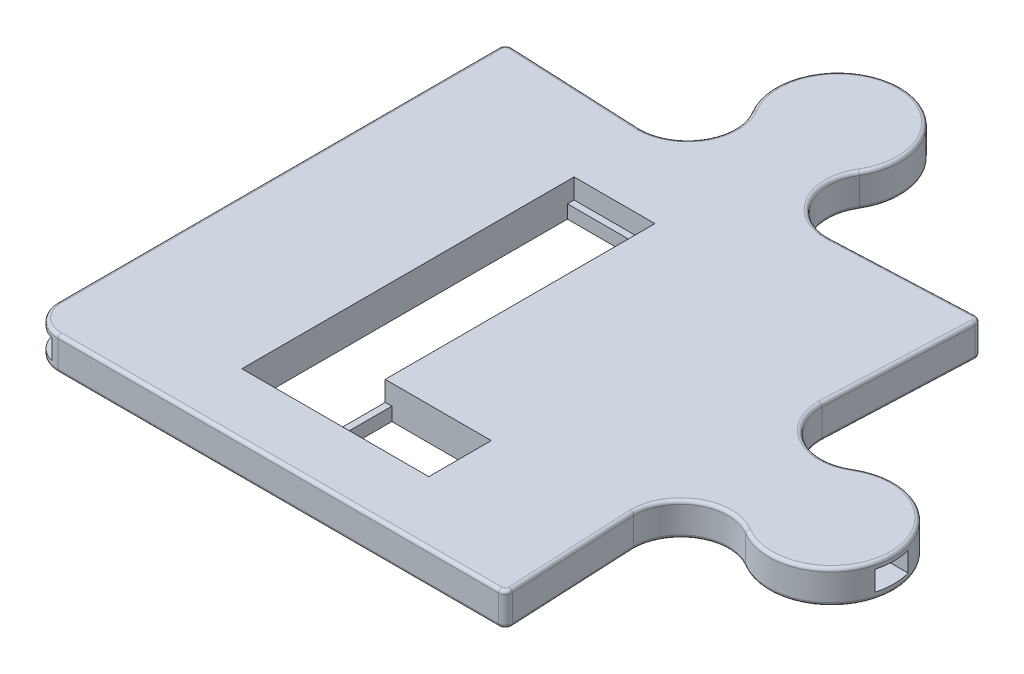
SolidWorks part; units mm, degrees
ref_plane "Front Plane" through (0, 0, 0) normal (0, 0, 1) x (1, 0, 0)
ref_plane "Top Plane" through (0, 0, 0) normal (0, 1, 0) x (1, 0, 0)
ref_plane "Right Plane" through (0, 0, 0) normal (1, 0, 0) x (0, 0, -1)
sketch "Sketch1" plane through (0, 0, 0) normal (0, 1, 0) x (1, 0, 0)
  line L0 (-31, -36) -> (37, -36) construction
  line L1 (-36, 37) -> (-36, -31) construction
  line L2 (-14.1421, 36) -> (-36, 37) construction
  line L3 (37, 37) -> (14.1421, 36) construction
  line L4 (36, 13.1421) -> (37, 37) construction
  line L5 (37, -36) -> (36, -15.1421) construction
  line L6 (-35.4, 36.3719) -> (-35.4, -31)
  line L7 (-36, 36) -> (36, 36) construction
  line L8 (-36, 36) -> (-36, -36) construction
  line L9 (-36, -36) -> (36, -36) construction
  line L10 (36, 36) -> (36, -36) construction
  line L11 (-31, -35.4) -> (36.3705, -35.4)
  line L12 (36.3705, -35.4) -> (35.4, -15.1568)
  line L13 (35.4, 13.155) -> (36.3732, 36.372)
  line L14 (36.3732, 36.372) -> (14.1555, 35.4)
  line L15 (-14.1562, 35.4) -> (-35.4, 36.3719)
  line L16 (-30, -24) -> (30, -24) construction
  line L17 (-30, 29) -> (30, 29) construction
  line L18 (-30, 29) -> (-30, -31) construction
  line L19 (-30, -31) -> (30, -31) construction
  line L20 (30, 29) -> (30, -31) construction
  line L21 (-30, 24) -> (30, 24) construction
  line L22 (-30, 24) -> (-30, -26) construction
  line L23 (-30, -26) -> (30, -26) construction
  line L24 (30, 24) -> (30, -26) construction
  arc A0 (-36, -31) -> (-31, -36) centre (-31, -31) ccw construction
  arc A1 (-14.1421, 36) -> (-8.571, 45.8485) centre (-14.1421, 42.5) ccw construction
  arc A2 (8.571, 45.8485) -> (-8.571, 45.8485) centre (0, 51) ccw construction
  arc A3 (8.571, 45.8485) -> (14.1421, 36) centre (14.1421, 42.5) ccw construction
  arc A4 (36, 13.1421) -> (45.8485, 7.571) centre (42.5, 13.1421) ccw construction
  arc A5 (45.8485, -9.571) -> (45.8485, 7.571) centre (51, -1) ccw construction
  arc A6 (45.8485, -9.571) -> (36, -15.1421) centre (42.5, -15.1421) ccw construction
  arc A7 (-35.4, -31) -> (-31, -35.4) centre (-31, -31) ccw
  arc A8 (46.1576, -9.0567) -> (35.4, -15.1568) centre (42.5, -15.1421) ccw
  arc A9 (46.1576, -9.0567) -> (46.1576, 7.0567) centre (51, -1) ccw
  arc A10 (35.4, 13.155) -> (46.1576, 7.0567) centre (42.5, 13.1421) ccw
  arc A11 (8.0567, 46.1576) -> (14.1555, 35.4) centre (14.1421, 42.5) ccw
  arc A12 (8.0567, 46.1576) -> (-8.0567, 46.1576) centre (0, 51) ccw
  arc A13 (-14.1562, 35.4) -> (-8.0567, 46.1576) centre (-14.1421, 42.5) ccw
  point P32 (36, 0)
  point P34 (0, 36)
  dimension "D5" = 6.5
  dimension "D6" = 10
  dimension "D7" = 6.5
  dimension "D13" = 5
  dimension "D9" = 10
  dimension "D11" = 6.5
  dimension "D12" = 6.5
  dimension "D1" = 72
  dimension "D2" = 1
  dimension "D3" = 1
  dimension "D4" = 15
  dimension "D8" = 1
  dimension "D10" = 35
  dimension "D14" = 15
  dimension "D15" = 36
  dimension "D16" = 1
  dimension "D18" = 60
  dimension "D19" = 60
  dimension "D20" = 5
  dimension "D21" = 6
  dimension "D22" = 5
  dimension "D23" = 50
  dimension "D24" = 2
  dimension "D17" = 0.6
extrude "Boss-Extrude1" add sketch "Sketch1" along normal blind 5
sketch "Sketch6" plane through (0, 0, 0) normal (0, -1, 0) x (1, 0, 0)
  line L0 (-35.4, -36.3719) -> (-35.4, 31) construction
  line L1 (-35.4, 17.9) -> (-27.4, 17.9)
  line L2 (-35.4, 17.9) -> (-35.4, -16.1)
  line L3 (-35.4, -16.1) -> (-27.4, -16.1)
  line L4 (-27.4, 17.9) -> (-27.4, -16.1)
  line L5 (-31, 35.4) -> (36.3705, 35.4) construction
  line L6 (-35.4, 14.65) -> (-30.4, 14.65)
  line L7 (-35.4, 14.65) -> (-35.4, -12.85)
  line L8 (-35.4, -12.85) -> (-30.4, -12.85)
  line L9 (-30.4, 14.65) -> (-30.4, -12.85)
  point P15 (-27.4, 0.9)
  point P16 (-30.4, 0.9)
  line M28 (-35.4, 31) -> (-35.4, -36.3719)
  dimension "D1" = 8
  dimension "D2" = 20.75
  dimension "D3" = 27.5
  dimension "D4" = 5
  dimension "D5" = 34
extrude "Cut-Extrude3" cut sketch "Sketch6" against normal blind 3 from offset 1 contours L6 L9 L8 L3 L4 L1 M28 | L9 L6 L2 L8 region at (-29.8665, 0, 0.9) region at (-32.9, 0, 0.9) offset against normal yes
extrude "Cut-Extrude4" cut sketch "Sketch6<3>" against normal up to next contours L9 L6 L2 L8 region at (-32.9, 0, 0.9)
sketch "Sketch6<3>" plane through (0, 0, 0) normal (0, -1, 0) x (1, 0, 0) same geometry as "Sketch6"
sketch "Sketch8" plane through (0, 0, 0) normal (0, -1, 0) x (1, 0, 0)
  line L1 (-2.5, -51.4) -> (2.5, -51.4)
  line L2 (-2.5, -51.4) -> (-2.5, -60.4)
  line L3 (-2.5, -60.4) -> (2.5, -60.4)
  line L4 (2.5, -51.4) -> (2.5, -60.4)
  line L5 (51.4, 3.5) -> (60.4, 3.5)
  line L6 (51.4, 3.5) -> (51.4, -1.5)
  line L7 (51.4, -1.5) -> (60.4, -1.5)
  line L8 (60.4, 3.5) -> (60.4, -1.5)
  arc A0 (-8.0567, -46.1576) -> (8.0567, -46.1576) centre (0, -51) ccw construction
  arc A1 (46.1576, -7.0567) -> (46.1576, 9.0567) centre (51, 1) ccw construction
  point P4 (0, -60.4)
  point P13 (60.4, 1)
  dimension "D1" = 5
  dimension "D2" = 9
  dimension "D3" = 5
  dimension "D4" = 9
extrude "Cut-Extrude5" cut sketch "Sketch8" against normal blind 3 from offset 1 offset against normal yes
sketch "Sketch9" plane through (0, 0, 0) normal (0, -1, 0) x (1, 0, 0)
  line L0 (-31, 35.4) -> (36.3705, 35.4) construction
  line L1 (-35.4, 14.65) -> (-35.4, 31) construction
  line L2 (-31.7636, 35.3332) -> (-35.4, 31) construction
  line L3 (-33.2571, 29.735) -> (-30.0429, 33.565) construction
  line L4 (-30.0429, 33.565) -> (-33.2571, 29.735) construction
  line L5 (-30.0429, 33.565) -> (-32.7119, 35.8048)
  line L6 (-33.2571, 29.735) -> (-35.926, 31.9747)
  line L7 (-32.7119, 35.8048) -> (-35.926, 31.9747)
  circle A0 centre (-31.65, 31.65) radius 2.5
  arc A1 (-31, 35.4) -> (-35.4, 31) centre (-31, 31) ccw construction
  arc M41 (-31, 35.4) -> (-35.4, 31) centre (-31, 31) ccw
  dimension "D1" = 5
  dimension "D3" = 3.75
  dimension "D4" = 5.6569
  dimension "D2" = 3.75
extrude "Cut-Extrude6" cut sketch "Sketch9" against normal blind 3 from offset 1 contours A0 L5 L6 M41 | A0 L5 region at (-33.6239, 0, 33.3064) region at (-31.65, 0, 31.65) offset against normal yes
sketch "Sketch11" plane through (-35.4, 0, 0) normal (-1, 0, 0) x (0, 0, 1)
  line L0 (-13.155, 0) -> (-36.372, 0) construction
  line L1 (-25.1, 3) -> (-19.1, 3)
  line L2 (-25.1, 3) -> (-25.1, 1.5)
  line L3 (-25.1, 1.5) -> (-19.1, 1.5)
  line L4 (-19.1, 3) -> (-19.1, 1.5)
  line L5 (-16.1, 4) -> (-16.1, 1) construction
  line L6 (35.4, 0) -> (15.1568, 0) construction
  line L7 (20.9, 3) -> (26.9, 3)
  line L8 (20.9, 3) -> (20.9, 1.5)
  line L9 (20.9, 1.5) -> (26.9, 1.5)
  line L10 (26.9, 3) -> (26.9, 1.5)
  line L12 (17.9, 4) -> (17.9, 1) construction
  dimension "D1" = 3
  dimension "D2" = 1.5
  dimension "D3" = 3
  dimension "D4" = 6
  dimension "D5" = 3
  dimension "D6" = 1.5
  dimension "D7" = 6
  dimension "D8" = 3
fillet "Fillet1" radius 0.5 17 edges at (-35.4, 0, 22.825) (-34.1113, 0, 34.1113) (2.6853, 0, 35.4) (35.8853, 0, 25.2784) (38.9978, 0, 8.966) (60.4, 0, 1) (38.9986, 0, -6.9655) (35.8866, 0, -24.7635) (25.2643, 0, -35.886) (7.9657, 0, -38.9984) (0, 0, -60.4) (-7.9658, 0, -38.9981) (-24.7781, 0, -35.886) (-35.4, 0, -24.611) (-32.9, 0, -12.85) (-30.4, 0, 0.9) (-32.9, 0, 14.65)
fillet "Fillet2" radius 0.5 13 edges at (-7.9658, 5, -38.9981) (0, 5, -60.4) (7.9657, 5, -38.9984) (25.2643, 5, -35.886) (35.8866, 5, -24.7635) (38.9986, 5, -6.9655) (60.4, 5, 1) (38.9978, 5, 8.966) (35.8853, 5, 25.2784) (2.6853, 5, 35.4) (-34.1113, 5, 34.1113) (-35.4, 5, -2.686) (-24.7781, 5, -35.886)
fillet "Fillet3" radius 1 9 edges at (36.2202, 0.1464, -36.2187) (36.2202, 4.8536, -36.2187) (36.3732, 2.5, -36.372) (-35.2536, 0.1464, -36.2186) (-35.2536, 4.8536, -36.2186) (36.2169, 0.1464, 35.2536) (36.2169, 4.8536, 35.2536) (36.3705, 2.5, 35.4) (-35.4, 2.5, -36.3719)
extrude "Cut-Extrude9" cut sketch "Sketch11" against normal blind 3
chamfer "Chamfer1" distance 1 angle 50 2 edges at (-35.4, 1.5, 23.9) (-35.4, 1.5, -22.1) first distance on face at (-35.4, 2.25, -22.1)
sketch "Sketch12" plane through (0, 5, 0) normal (0, 1, 0) x (1, 0, 0)
  text T0 "L" font "Poppins" height 50
extrude "Cut-Extrude10" cut sketch "Sketch12" against normal through all
sketch "Sketch13" plane through (0, 0, 0) normal (0, -1, 0) x (1, 0, 0)
  line L0 (-0.5565, 16.6018) -> (15.406, 16.6018) construction
  line L1 (15.406, 26) -> (14.406, 26)
  line L2 (15.406, 26) -> (15.406, 16.6018)
  line L3 (15.406, 16.6018) -> (14.406, 16.6018)
  line L4 (14.406, 26) -> (14.406, 16.6018)
  line L6 (-0.5565, 16.6018) -> (0.4435, 16.6018)
  line L7 (-0.5565, 16.6018) -> (-0.5565, 26)
  line L8 (-0.5565, 26) -> (0.4435, 26)
  line L9 (0.4435, 16.6018) -> (0.4435, 26)
  line L10 (-12.7267, 26) -> (-12.7267, -24) construction
  line L11 (-0.5565, -24) -> (-12.7267, -24)
  line L12 (-0.5565, -24) -> (-0.5565, -23)
  line L13 (-0.5565, -23) -> (-12.7267, -23)
  line L14 (-12.7267, -24) -> (-12.7267, -23)
  line L15 (15.406, 26) -> (-12.7267, 26) construction
  line L17 (-12.7267, 26) -> (15.406, 26)
  line L18 (-12.7267, 26) -> (-12.7267, 25)
  line L19 (-12.7267, 25) -> (15.406, 25)
  line L20 (15.406, 26) -> (15.406, 25)
  line M28 (-0.5565, 16.6018) -> (-0.5565, -24)
  line M29 (-0.5565, -24) -> (-12.7267, -24)
  line M30 (-12.7267, -24) -> (-12.7267, 26)
  line M31 (-12.7267, 26) -> (15.406, 26)
  line M33 (15.406, 16.6018) -> (-0.5565, 16.6018)
  dimension "D1" = 1
  dimension "D2" = 1
  dimension "D3" = 1
  dimension "D4" = 1
extrude "Boss-Extrude2" add sketch "Sketch13" against normal blind 2 contours L13 M28 M30 M29 | L19 L7 M30 M31 | L7 L19 L9 M31 | L19 L7 L9 M33 | L17 L18 L19 L20 region at (-0.0565, 0, 25.5) region at (-0.0565, 0, 20.8009) region at (-6.6416, 0, 25.5) region at (-6.6416, 0, -23.5)
